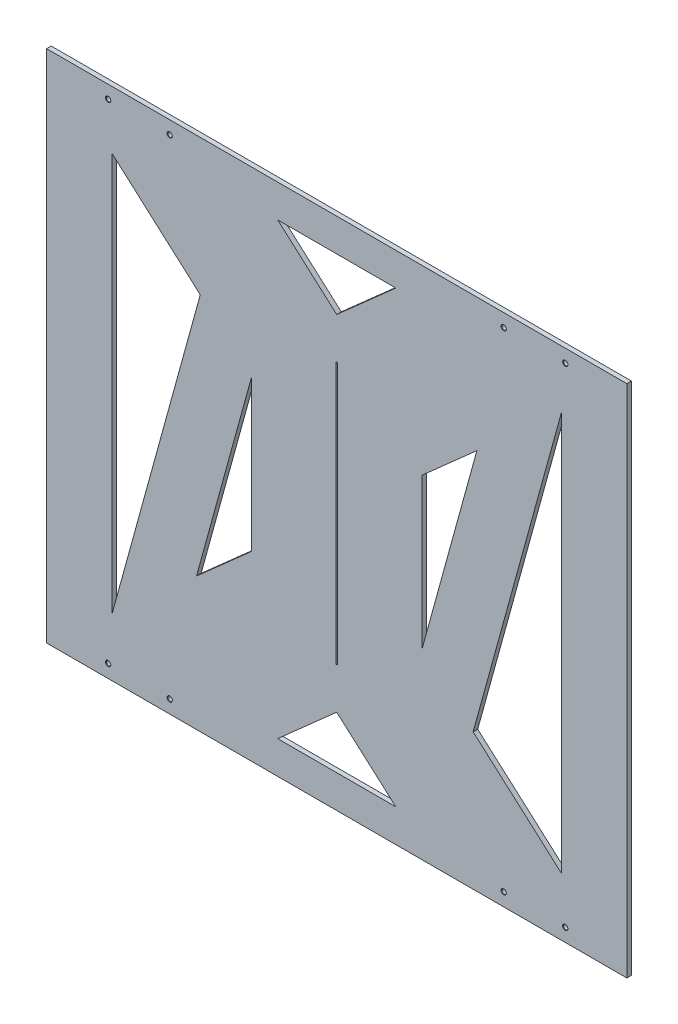
SolidWorks part; units mm, degrees
material "3.0205 (EN-AW 1200)"
ref_plane "Piano frontale" through (0, 0, 0) normal (0, 0, 1) x (1, 0, 0)
ref_plane "Piano superiore" through (0, 0, 0) normal (0, 1, 0) x (1, 0, 0)
ref_plane "Piano destro" through (0, 0, 0) normal (1, 0, 0) x (0, 0, -1)
sketch "Schizzo1" plane through (0, 0, 0) normal (0, 0, 1) x (1, 0, 0)
  line L1 (-443, -393) -> (443, -393)
  line L2 (-443, -393) -> (-443, 393)
  line L3 (-443, 393) -> (443, 393)
  line L4 (443, -393) -> (443, 393)
  line L5 (-443, -393) -> (443, 393) construction
  line L6 (-443, 393) -> (443, -393) construction
  point P0 (0, 0)
  dimension "D1" = 886
  dimension "D2" = 786
extrude "Estrusione-Estrusione1" add sketch "Schizzo1" along normal blind 7
hole_wizard "Foro filettato M8-1" positions "Schizzo8" profile "Schizzo10" tap size "M8" standard "ISO"
sketch "Schizzo8" plane through (0, 0, 7) normal (0, 0, 1) x (1, 0, 0)
  line L0 (-443, 373) -> (443, 373) construction
  line L1 (-443, 393) -> (-443, -393) construction
  line L2 (443, -393) -> (443, 393) construction
  line L4 (443, 393) -> (-443, 393) construction
  line L6 (-443, -373) -> (443, -373) construction
  line L8 (-443, -393) -> (443, -393) construction
  line L9 (-349, 373) -> (-349, -373) construction
  line L11 (-255, 373) -> (-255, -373) construction
  line L13 (255, 373) -> (255, -373) construction
  line L15 (349, 373) -> (349, -373) construction
  point P0 (-349, 373)
  point P2 (-255, 373)
  point P4 (255, 373)
  point P6 (349, 373)
  point P8 (-349, -373)
  point P10 (-255, -373)
  point P14 (349, -373)
  point P16 (255, -373)
  dimension "D1" = 20
  dimension "D2" = 20
  dimension "D3" = 94
  dimension "D4" = 94
  dimension "D5" = 94
  dimension "D6" = 94
sketch "Schizzo10" plane through (-349, 373, 7) normal (1, 0, 0) x (0, -1, 0)
  line L0 (0, 0) -> (0, 24.2929)
  line L1 (0, 24.2929) -> (3.4, 22.25)
  line L2 (3.4, 22.25) -> (3.4, 0.625)
  line L3 (3.4, 0.625) -> (4.025, 0)
  line L5 (4.025, 0) -> (0, 0)
  line L6 (-3.4, 0.625) -> (-4.025, 0) construction
  line L10 (0, 24.2929) -> (-3.4, 22.25) construction
  line L11 (0, -6.35) -> (0, 107.95) construction
  dimension "Tap Drill Dia." = 6.8
  dimension "Tap Drill Depth" = 22.25
  dimension "Near C'Sink Dia." = 8.05
  dimension "Near C'Sink Angle" = 90
  dimension "Drill Angle" = 118
cosmetic thread "Filettatura del foro1" parameters "D1"=16, "D2"=8
cosmetic thread "Filettatura del foro2" parameters "D1"=16, "D2"=8
cosmetic thread "Filettatura del foro3" parameters "D1"=16, "D2"=8
cosmetic thread "Filettatura del foro4" parameters "D1"=16, "D2"=8
cosmetic thread "Filettatura del foro5" parameters "D1"=16, "D2"=8
cosmetic thread "Filettatura del foro6" parameters "D1"=16, "D2"=8
cosmetic thread "Filettatura del foro7" parameters "D1"=16, "D2"=8
cosmetic thread "Filettatura del foro8" parameters "D1"=16, "D2"=8
sketch "Schizzo11" plane through (0, 0, 7) normal (0, 0, 1) x (1, 0, 0)
  line L1 (-1, 200) -> (1, 200)
  line L2 (-1, 200) -> (-1, -200)
  line L3 (-1, -200) -> (1, -200)
  line L4 (1, 200) -> (1, -200)
  line L5 (-1, 200) -> (1, -200) construction
  line L6 (-1, -200) -> (1, 200) construction
  point P0 (0, 0)
  dimension "D1" = 400
  dimension "D2" = 2
extrude "Taglio-Estrusione1" cut sketch "Schizzo11" against normal blind 5
sketch "Schizzo12" plane through (0, 0, 7) normal (0, 0, 1) x (1, 0, 0)
  line L0 (-443, 393) -> (443, -393) construction
  line L1 (443, 393) -> (-443, -393) construction
  line L2 (-343, 304.2867) -> (-343, -304.2867)
  line L3 (-343, -304.2867) -> (-208.349, 184.8333)
  line L4 (-208.349, 184.8333) -> (-343, 304.2867)
  line L5 (-130, 115.3273) -> (-214.0159, -189.8606)
  line L6 (-214.0159, -189.8606) -> (-130, -115.3273)
  line L7 (-130, -115.3273) -> (-130, 115.3273)
  line L8 (0, 393) -> (0, -393) construction
  line L9 (443, 393) -> (-443, 393) construction
  line L10 (-443, -393) -> (443, -393) construction
  line L11 (-443, 393) -> (-443, -393) construction
  line L12 (343, -304.2867) -> (208.349, -184.8333)
  line L13 (208.349, -184.8333) -> (343, 304.2867)
  line L14 (343, 304.2867) -> (343, -304.2867)
  line L15 (130, -115.3273) -> (214.0159, 189.8606)
  line L16 (214.0159, 189.8606) -> (130, 115.3273)
  line L17 (130, 115.3273) -> (130, -115.3273)
  line L18 (443, -393) -> (443, 393) construction
  line L19 (-90.1781, 343) -> (90.1781, 343)
  line L20 (90.1781, 343) -> (0, 263)
  line L21 (0, 263) -> (-90.1781, 343)
  line L22 (-90.1781, -343) -> (90.1781, -343)
  line L23 (90.1781, -343) -> (0, -263)
  line L24 (0, -263) -> (-90.1781, -343)
  dimension "D1" = 100
  dimension "D2" = 130
  dimension "D3" = 180
  dimension "D4" = 100
  dimension "D5" = 130
  dimension "D6" = 180
  dimension "D7" = 50
  dimension "D8" = 80
  dimension "D9" = 80
  dimension "D10" = 50
extrude "Taglio-Estrusione2" cut sketch "Schizzo12" against normal through all
